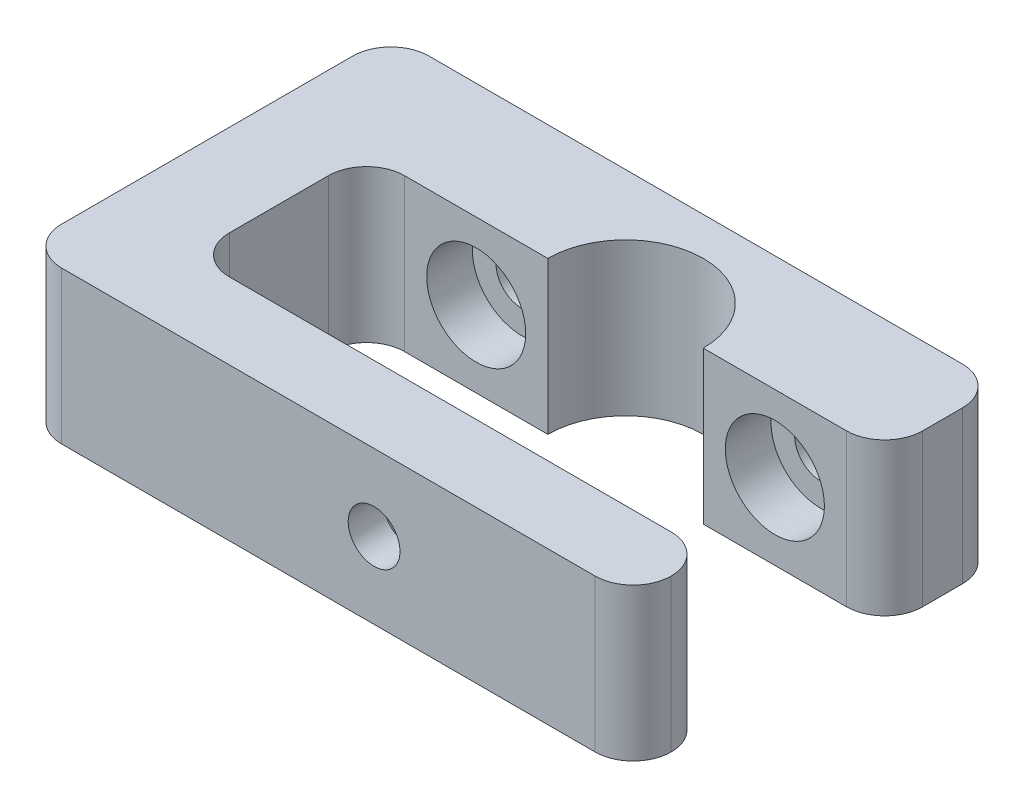
SolidWorks part; units mm, degrees
ref_plane "Front Plane" through (0, 0, 0) normal (0, 0, 1) x (1, 0, 0)
ref_plane "Top Plane" through (0, 0, 0) normal (0, 1, 0) x (1, 0, 0)
ref_plane "Right Plane" through (0, 0, 0) normal (1, 0, 0) x (0, 0, -1)
sketch "Sketch1" plane through (0, 0, 0) normal (0, 1, 0) x (1, 0, 0)
  line L0 (5.1, 0) -> (17, 0)
  line L1 (17, 0) -> (17, 7.6)
  line L2 (17, 7.6) -> (-23, 7.6)
  line L3 (-5.1, 0) -> (-17, 0)
  line L4 (-17, 0) -> (-17, -11.5)
  line L5 (-17, -11.5) -> (17, -11.5)
  line L6 (17, -11.5) -> (17, -16.5)
  line L7 (17, -16.5) -> (-23, -16.5)
  line L8 (-23, -16.5) -> (-23, 7.6)
  arc A0 (5.1, 0) -> (-5.1, 0) centre (0, 0) ccw
  point P1 (0, 5.1)
  dimension "D1" = 10.2
  dimension "D2" = 11.5
  dimension "D3" = 6
  dimension "D4" = 2.5
  dimension "D5" = 40
  dimension "D6" = 5
extrude "Boss-Extrude1" add sketch "Sketch1" along normal blind 10
fillet "Fillet1" radius 2.5 8 edges at (-23, 5, -7.6) (-17, 5, 0) (-17, 5, 11.5) (-23, 5, 16.5) (17, 5, 16.5) (17, 5, 11.5) (17, 5, 0) (17, 5, -7.6)
sketch "Sketch3" plane through (0, 0, 11.5) normal (0, 0, -1) x (-1, 0, 0)
  line L0 (0, 10) -> (0, 0) construction
  line L1 (-14.5, 10) -> (14.5, 10) construction
  line L2 (-14.5, 0) -> (14.5, 0) construction
  line L3 (-14.5, 5) -> (14.5, 5) construction
  line L4 (-14.5, 10) -> (-14.5, 0) construction
  line L5 (14.5, 0) -> (14.5, 10) construction
  line L7 (3.3, 5) -> (1.65, 7.8579)
  line L8 (1.65, 7.8579) -> (-1.65, 7.8579)
  line L9 (-1.65, 7.8579) -> (-3.3, 5)
  line L10 (-3.3, 5) -> (-1.65, 2.1421)
  line L11 (-1.65, 2.1421) -> (1.65, 2.1421)
  line L12 (1.65, 2.1421) -> (3.3, 5)
  circle A0 centre (0, 5) radius 2.8579 construction
  dimension "D1" = 3.3
extrude "Cut-Extrude1" cut sketch "Sketch3" against normal blind 2.7
sketch "Sketch4" plane through (0, 0, 0) normal (0, 0, 1) x (1, 0, 0)
  line L0 (-9.8, 10) -> (-9.8, 0) construction
  line L1 (-14.5, 10) -> (-5.1, 10) construction
  line L2 (-14.5, 0) -> (-5.1, 0) construction
  line L3 (9.8, 10) -> (9.8, 0) construction
  line L4 (5.1, 10) -> (14.5, 10) construction
  line L5 (5.1, 0) -> (14.5, 0) construction
  line L6 (-14.5, 5) -> (-5.1, 5) construction
  line L7 (-14.5, 10) -> (-14.5, 0) construction
  line L8 (-5.1, 10) -> (-5.1, 0) construction
  line L9 (5.1, 5) -> (14.5, 5) construction
  line L10 (5.1, 10) -> (5.1, 0) construction
  line L11 (14.5, 0) -> (14.5, 10) construction
  point P24 (-9.8, 5)
  point P25 (9.8, 5)
hole_wizard "CBORE for M3 SHCS1" positions "Sketch5" profile "Sketch6" counterbore size "M3" standard "ANSI Metric" end condition through all
sketch "Sketch5" plane through (0, 0, 0) normal (0, 0, 1) x (1, 0, 0)
  point P0 (-9.8, 5)
  point P3 (9.8, 5)
sketch "Sketch6" plane through (-9.8, 5, 0) normal (1, 0, 0) x (0, -1, 0)
  line L0 (0, 0) -> (0, 7.6)
  line L1 (0, 7.6) -> (1.7, 7.6)
  line L3 (1.7, 7.6) -> (1.7, 3)
  line L4 (1.7, 3) -> (3.25, 3)
  line L5 (3.25, 3) -> (3.25, 0)
  line L7 (3.25, 0) -> (0, 0)
  line L11 (0, -6.35) -> (0, 107.95) construction
  dimension "Thru Hole Dia." = 3.4
  dimension "Thru Hole Depth" = 7.6
  dimension "C'Bore Dia." = 6.5
  dimension "C'Bore Depth" = 3
sketch "Sketch9" plane through (0, 0, 14.2) normal (0, 0, -1) x (-1, 0, 0)
  line L0 (0, 2.1421) -> (0, 7.8579) construction
  line L1 (-1.65, 2.1421) -> (1.65, 2.1421) construction
  line L2 (-3.3, 5) -> (3.3, 5) construction
  line L3 (-3.3, 5) -> (-1.65, 2.1421) construction
  line L4 (1.65, 7.8579) -> (-1.65, 7.8579) construction
  point P16 (0, 5)
hole_wizard "M3 Clearance Hole1" positions "Sketch10" profile "Sketch11" hole size "M3" standard "ANSI Metric" end condition through all
sketch "Sketch10" plane through (0, 0, 14.2) normal (0, 0, -1) x (-1, 0, 0)
  point P0 (0, 5)
sketch "Sketch11" plane through (0, 5, 14.2) normal (1, 0, 0) x (0, 1, 0)
  line L0 (0, 0) -> (0, 2.3)
  line L1 (0, 2.3) -> (1.7, 2.3)
  line L2 (1.7, 2.3) -> (1.7, 0)
  line L5 (1.7, 0) -> (0, 0)
  line L11 (0, -6.35) -> (0, 107.95) construction
  dimension "Thru Hole Dia." = 3.4
  dimension "Thru Hole Depth" = 2.3
